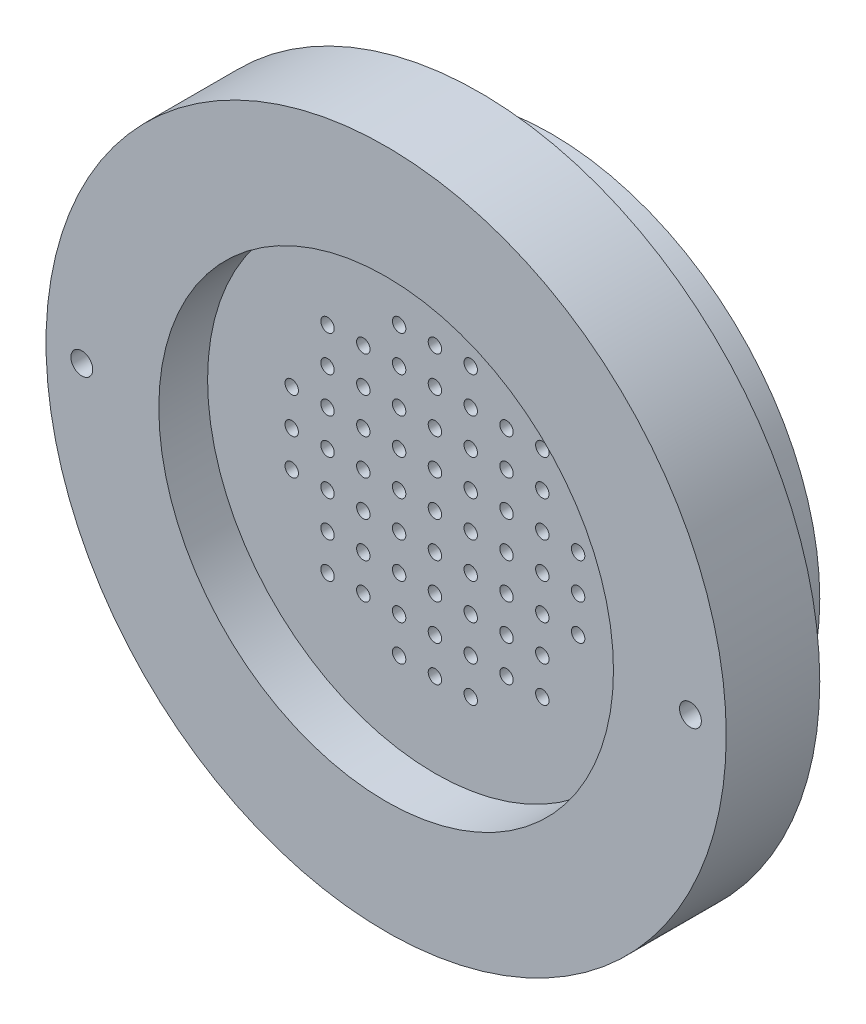
SolidWorks part; units mm, degrees
ref_plane "Plan de face" through (0, 0, 0) normal (0, 0, 1) x (1, 0, 0)
ref_plane "Plan de dessus" through (0, 0, 0) normal (0, 1, 0) x (1, 0, 0)
ref_plane "Plan de droite" through (0, 0, 0) normal (1, 0, 0) x (0, 0, -1)
sketch "Sketch1" plane through (0, 0, 0) normal (0, 0, 1) x (1, 0, 0)
  circle A0 centre (0, 0) radius 38
extrude "Boss-Extrude1" add sketch "Sketch1" along normal blind 5
sketch "Sketch2" plane through (0, 0, 5) normal (0, 0, 1) x (1, 0, 0)
  circle A0 centre (0, 0) radius 0.75
extrude "Cut-Extrude1" cut sketch "Sketch2" against normal through all
pattern_linear "LPattern1" count 5 spacing 4 along (0, 1, 0) count 5 spacing 4 along (1, 0, 0) skipping (2, 4), (3, 4), (4, 2), (4, 3), (4, 4) of "Cut-Extrude1"
mirror "Mirror1" about plane through (0, 0, 0) normal (1, 0, 0) of "LPattern1" second plane through (0, 0, 0) second plane normal (0, 1, 0)
sketch "Sketch16" plane through (0, 0, 5) normal (0, 0, 1) x (1, 0, 0)
  circle A0 centre (0, 0) radius 25.4
  circle A1 centre (0, 0) radius 38
extrude "Boss-Extrude2" add sketch "Sketch16" along normal blind 5.45
sketch "Sketch17" plane through (0, 0, 0) normal (0, 0, -1) x (-1, 0, 0)
  circle A0 centre (0, 0) radius 25.4
  circle A1 centre (0, 0) radius 30
extrude "Boss-Extrude3" add sketch "Sketch17" along normal blind 8
sketch "Sketch20" plane through (0, 0, 0) normal (0, 0, -1) x (-1, 0, 0)
  line L0 (-30, 0) -> (-38, 0)
  circle A0 centre (0, 0) radius 30 construction
  circle A1 centre (0, 0) radius 38 construction
hole_wizard "CBORE for #2 Binding Head Machine Screw1" positions "Sketch24" profile "Sketch25" counterbore size "#2" standard "ANSI Inch" end condition through all
sketch "Sketch24" plane through (0, 0, 0) normal (0, 0, -1) x (-1, 0, 0)
  line L0 (-30, 0) -> (-38, 0) construction
  point P0 (-34, 0)
sketch "Sketch25" plane through (34, 0, 0) normal (1, 0, 0) x (0, 1, 0)
  line L0 (0, 0) -> (0, 10.45)
  line L1 (0, 10.45) -> (1.2192, 10.45)
  line L3 (1.2192, 10.45) -> (1.2192, 1.27)
  line L4 (1.2192, 1.27) -> (2.7788, 1.27)
  line L5 (2.7788, 1.27) -> (2.7788, 0)
  line L7 (2.7788, 0) -> (0, 0)
  line L11 (0, -6.35) -> (0, 107.95) construction
  dimension "Thru Hole Dia." = 2.4384
  dimension "Thru Hole Depth" = 10.45
  dimension "C'Bore Dia." = 5.5575
  dimension "C'Bore Depth" = 1.27
mirror "Mirror2" about plane through (0, 0, 0) normal (1, 0, 0) of "CBORE for #2 Binding Head Machine Screw1"
